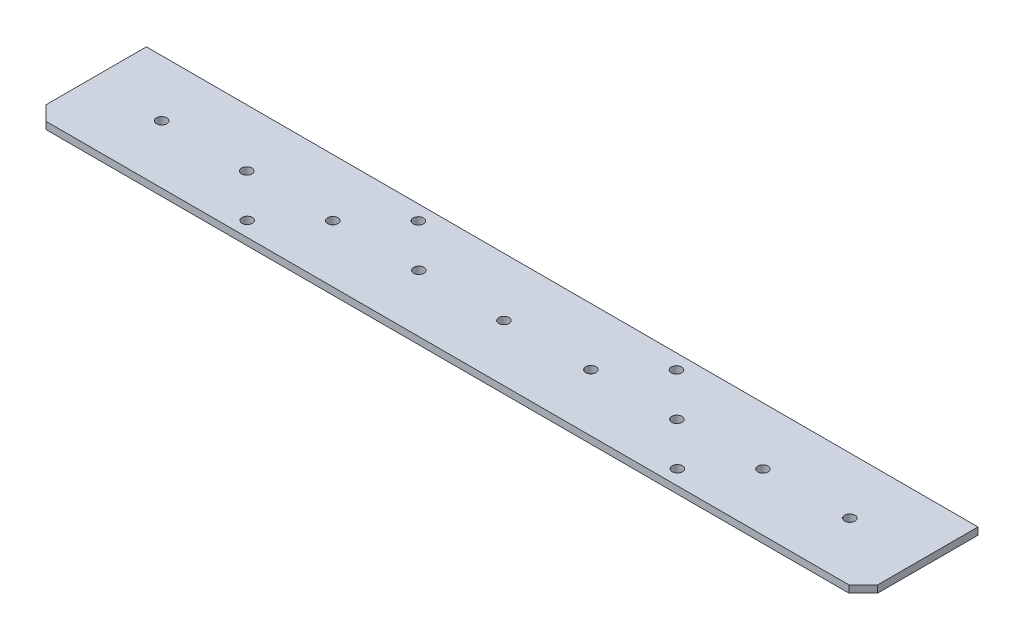
SolidWorks part; units mm, degrees
ref_plane "Front Plane" through (0, 0, 0) normal (0, 0, 1) x (1, 0, 0)
ref_plane "Top Plane" through (0, 0, 0) normal (0, 1, 0) x (1, 0, 0)
ref_plane "Right Plane" through (0, 0, 0) normal (1, 0, 0) x (0, 0, -1)
sketch "Sketch2" plane through (0, 0, 0) normal (0, 1, 0) x (1, 0, 0)
  line L0 (0, 0) -> (0, 50.8)
  line L1 (0, 50.8) -> (368.3, 50.8)
  line L2 (368.3, 50.8) -> (368.3, 0)
  line L3 (368.3, 0) -> (0, 0)
  dimension "D1" = 50.8
  dimension "D2" = 368.3
extrude "Boss-Extrude1" add sketch "Sketch2" along normal blind 3.175
sketch "Sketch3" plane through (0, 3.175, 0) normal (0, 1, 0) x (1, 0, 0)
  line L0 (184.15, 0) -> (184.15, 50.8) construction
  line L1 (0, 0) -> (368.3, 0) construction
  line L2 (368.3, 50.8) -> (0, 50.8) construction
  line L3 (31.75, 25.7969) -> (184.15, 25.0031) construction
  line L4 (336.55, 25.7969) -> (184.15, 25.0031) construction
  line L5 (0, 6.35) -> (6.35, 0)
  line L6 (6.35, 0) -> (0, 0)
  line L7 (0, 0) -> (0, 6.35)
  line L8 (361.95, 0) -> (368.3, 0)
  line L9 (368.3, 6.35) -> (361.95, 0)
  line L10 (368.3, 0) -> (368.3, 6.35)
  line L11 (241.3, 44.2526) -> (279.4, 6.5474) construction
  circle A0 centre (184.15, 25.0031) radius 2.286
  circle A1 centre (31.75, 25.7969) radius 2.286
  circle A2 centre (107.95, 25.4) radius 2.286
  circle A3 centre (69.85, 25.4) radius 2.286
  circle A4 centre (146.05, 25.4) radius 2.286
  circle A5 centre (222.25, 25.4) radius 2.286
  circle A6 centre (298.45, 25.4) radius 2.286
  circle A7 centre (260.35, 25.4) radius 2.286
  circle A8 centre (336.55, 25.7969) radius 2.286
  circle A9 centre (241.3, 44.2526) radius 2.286
  circle A10 centre (279.4, 6.5474) radius 2.286
  circle A11 centre (88.9, 6.5474) radius 2.286
  circle A12 centre (127, 44.2526) radius 2.286
  point P33 (278.5483, 11.8754)
  point P37 (260.35, 25.4)
  point P38 (246.3141, 39.2905)
  dimension "D1" = 4.572
  dimension "D2" = 0.7937
  dimension "D6" = 25.4
  dimension "D3" = 152.4
  dimension "D4" = 38.1
  dimension "D5" = 38.1
  dimension "D7" = 6.35
  dimension "D8" = 6.35
  dimension "D9" = 45
  dimension "D10" = 19.05
extrude "Cut-Extrude1" cut sketch "Sketch3" against normal up to next
